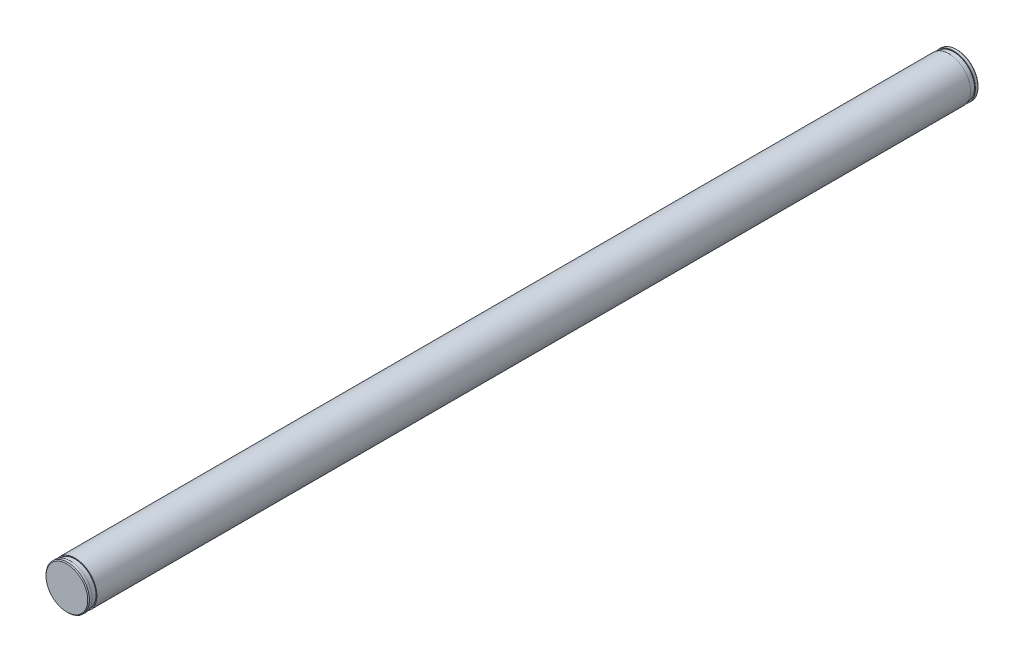
SolidWorks part; units mm, degrees
ref_plane "Vorne" through (0, 0, 0) normal (0, 0, 1) x (1, 0, 0)
ref_plane "Oben" through (0, 0, 0) normal (0, 1, 0) x (1, 0, 0)
ref_plane "Seite" through (0, 0, 0) normal (1, 0, 0) x (0, 0, -1)
sketch "Skizze1" plane through (0, 0, 0) normal (0, 0, 1) x (1, 0, 0)
  circle A0 centre (0, 0) radius 5
  dimension "D1" = 10
sketch "Skizze7" plane through (0, 0, 0) normal (1, 0, 0) x (0, 0, -1)
  line L0 (-204, 5) -> (-204, 4.8)
  line L1 (50, 0) -> (-50, 0) construction
  line L2 (-204, 4.8) -> (-202.9, 4.8)
  line L3 (-202.9, 4.8) -> (-202.9, 5)
  line L5 (-1.9, 5) -> (-1.9, 4.8)
  line L6 (-1.9, 4.8) -> (-0.8, 4.8)
  line L7 (-0.8, 4.8) -> (-0.8, 5)
  line L10 (-204.8, 0) -> (0, 0)
  line L11 (0, 50) -> (0, -50) construction
  line L12 (-202.9, 5) -> (-1.9, 5)
  line L13 (-204, 5) -> (-204.8, 5)
  line L14 (-204.8, 5) -> (-204.8, 0)
  line L16 (0, 0) -> (0, 5)
  line L17 (0, 5) -> (-0.8, 5)
  point P2 (0, 0)
  point P3 (0, 0)
  dimension "D1" = 0.2
  dimension "D2" = 1.1
  dimension "D4" = 201
  dimension "D5" = 0.8
  dimension "D3" = 4.8
revolve "Rotation1" add sketch "Skizze7" angle 360 about L10
chamfer "Fase1" distance 0.2 angle 45 2 edges at (5, 0, 0) (5, 0, 204.8)
equation "\"d1\"= 10mm"
equation "\"D1@Skizze1\"= \"d1\""
equation "\"n\"= 0.6mm"
equation "\"m\"= 1.1mm"
equation "\"d2\"= 9.6mm"
equation "\"D2@Skizze7\"= \"m\""
equation "\"D1@Skizze7\" = ( \"d1\" - \"d2\" ) / 2"
